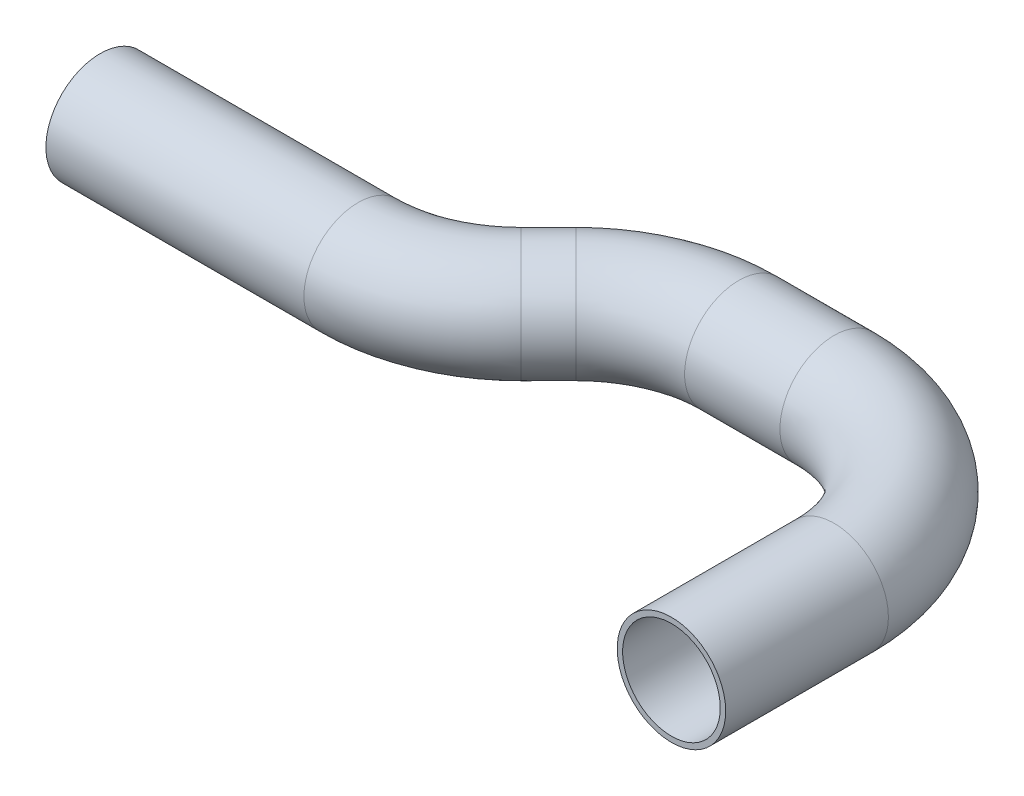
SolidWorks part; units mm, degrees
ref_plane "Front Plane" through (0, 0, 0) normal (0, 0, 1) x (1, 0, 0)
ref_plane "Top Plane" through (0, 0, 0) normal (0, 1, 0) x (1, 0, 0)
ref_plane "Right Plane" through (0, 0, 0) normal (1, 0, 0) x (0, 0, -1)
sketch "Sketch1" plane through (0, 0, 0) normal (0, 1, 0) x (1, 0, 0)
  line L0 (0, 0) -> (30.2092, 0)
  line L1 (43.6796, 5.5796) -> (46.9142, 8.8142)
  line L2 (60.3846, 14.3939) -> (71.5439, 14.3939)
  line L3 (90.5939, -4.6561) -> (90.5939, -23.7061)
  arc A0 (71.5439, 14.3939) -> (90.5939, -4.6561) centre (71.5439, -4.6561) cw
  arc A1 (46.9142, 8.8142) -> (60.3846, 14.3939) centre (60.3846, -4.6561) cw
  arc A2 (30.2092, 0) -> (43.6796, 5.5796) centre (30.2092, 19.05) ccw
  point P7 (90.5939, 14.3939)
  point P10 (52.4939, 14.3939)
  point P14 (38.1, 0)
  dimension "D6" = 19.05
  dimension "D1" = 38.1
  dimension "D2" = 38.1
  dimension "D3" = 38.1
  dimension "D4" = 45
  dimension "D5" = 14.3939
ref_plane "Plane1" through (0, 0, 0) normal (1, 0, 0) x (0, 0, -1)
sketch "Sketch2" plane through (0, 0, 0) normal (1, 0, 0) x (0, 0, -1)
  circle A0 centre (0, 0) radius 6.35
  circle A1 centre (0, 0) radius 5.715
  dimension "D1" = 12.7
  dimension "D2" = 0.635
sweep "Sweep1" add profiles "Sketch2" path "Sketch1"
